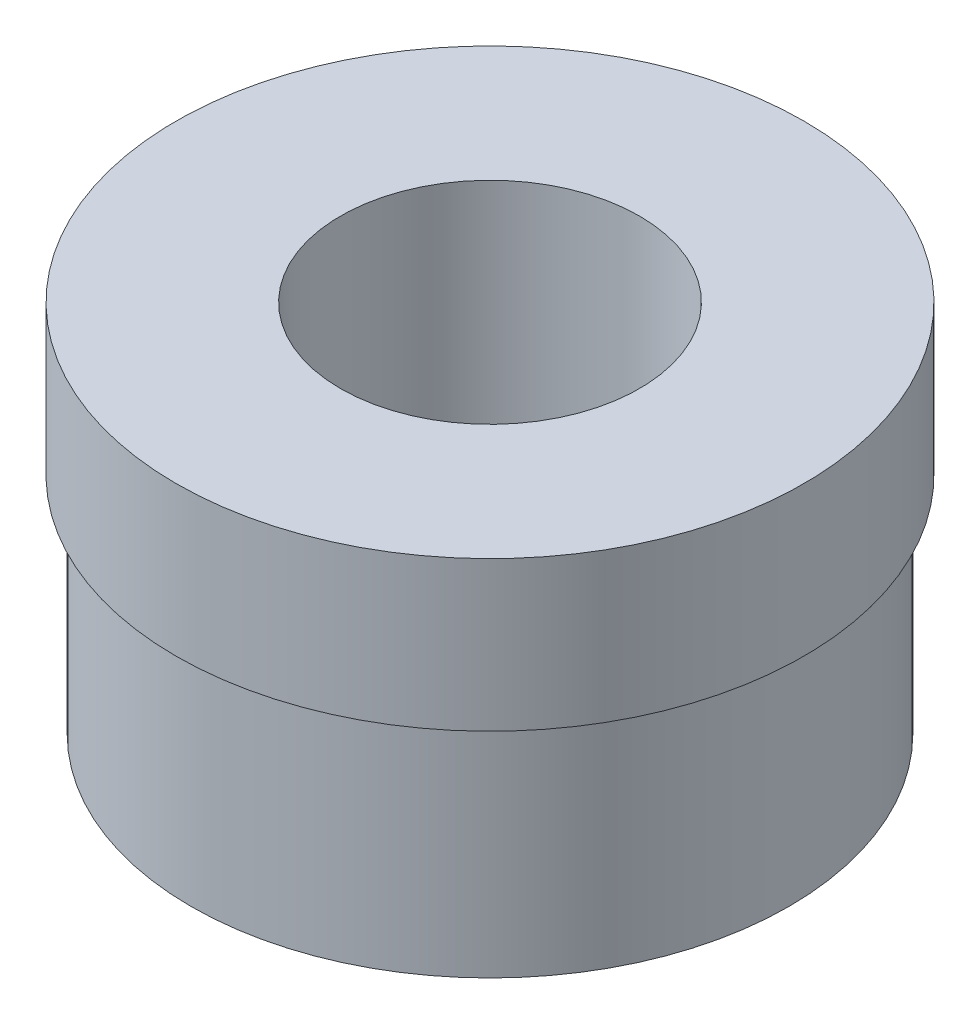
SolidWorks part; units mm, degrees
material "Plain Carbon Steel"
ref_plane "Front Plane" through (0, 0, 0) normal (0, 0, 1) x (1, 0, 0)
ref_plane "Top Plane" through (0, 0, 0) normal (0, 1, 0) x (1, 0, 0)
ref_plane "Right Plane" through (0, 0, 0) normal (1, 0, 0) x (0, 0, -1)
sketch "Sketch1" plane through (0, 0, 0) normal (0, 0, 1) x (1, 0, 0)
  line L0 (0, 61.8349) -> (0, -68.8073) construction
  line L1 (10, 0) -> (10, 25)
  line L2 (21, 25) -> (21, 15)
  line L3 (21, 15) -> (20, 15)
  line L4 (20, 15) -> (20, 0)
  line L5 (20, 0) -> (10, 0)
  line L6 (10, 25) -> (21, 25)
  dimension "D1" = 20
  dimension "D2" = 40
  dimension "D3" = 25
  dimension "D4" = 10
  dimension "D5" = 42
revolve "Revolve1" add sketch "Sketch1" angle 360 about L0
